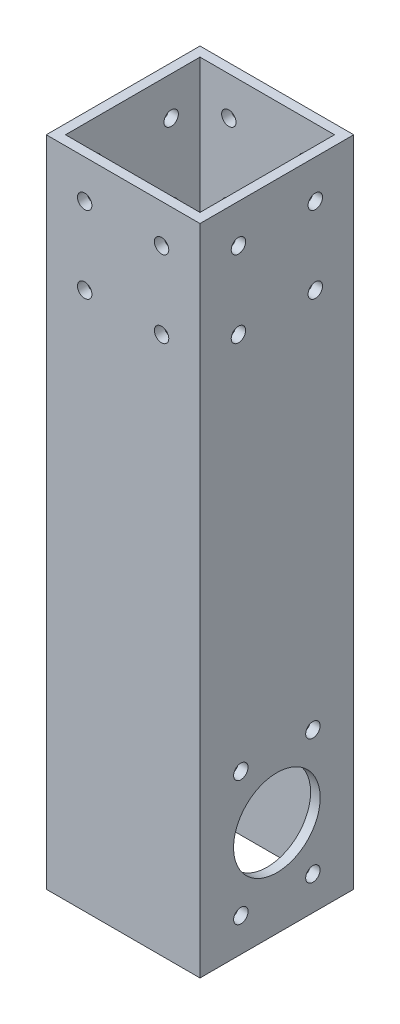
SolidWorks part; units mm, degrees
material "6063-T1"
ref_plane "Front Plane" through (0, 0, 0) normal (0, 0, 1) x (1, 0, 0)
ref_plane "Top Plane" through (0, 0, 0) normal (0, 1, 0) x (1, 0, 0)
ref_plane "Right Plane" through (0, 0, 0) normal (1, 0, 0) x (0, 0, -1)
sketch "Sketch1" plane through (0, 0, 0) normal (0, 1, 0) x (1, 0, 0)
  line L1 (-25.4, 25.4) -> (25.4, 25.4)
  line L2 (-25.4, 25.4) -> (-25.4, -25.4)
  line L3 (-25.4, -25.4) -> (25.4, -25.4)
  line L4 (25.4, 25.4) -> (25.4, -25.4)
  line L5 (-25.4, 25.4) -> (25.4, -25.4) construction
  line L6 (-25.4, -25.4) -> (25.4, 25.4) construction
  point P0 (0, 0)
  dimension "D1" = 50.8
  dimension "D2" = 50.8
extrude "Boss-Extrude1" add sketch "Sketch1" along normal blind 215.9
shell "Shell1" thickness 3.175 removed face at (0, 0, 0) removed face at (0, 215.9, 0)
sketch "Sketch2" plane through (25.4, 0, 0) normal (1, 0, 0) x (0, 0, -1)
  line L0 (-25.4, 0) -> (25.4, 0) construction
  circle A0 centre (0, 31.75) radius 14.3129
  dimension "D1" = 28.6258
  dimension "D2" = 31.75
extrude "Cut-Extrude1" cut sketch "Sketch2" against normal through all
sketch "Sketch3" plane through (25.4, 0, 0) normal (1, 0, 0) x (0, 0, -1)
  line L0 (0, 0) -> (0, 31.75) construction
  line L1 (-25.4, 0) -> (25.4, 0) construction
  line L2 (0, 31.75) -> (-11.9063, 52.3722) construction
  circle A0 centre (0, 31.75) radius 23.8125 construction
  circle A1 centre (-11.9063, 52.3722) radius 2.3812
  circle A2 centre (11.9062, 52.3722) radius 2.3812
  circle A3 centre (23.8125, 31.75) radius 2.3812
  circle A4 centre (11.9063, 11.1278) radius 2.3812
  circle A5 centre (-11.9062, 11.1278) radius 2.3813
  circle A6 centre (-23.8125, 31.75) radius 2.3812
  point P21 (0, 31.75)
  dimension "D1" = 47.625
  dimension "D2" = 4.7625
  dimension "D3" = 150
  dimension "D4" = 6
extrude "Cut-Extrude2" cut sketch "Sketch3" against normal through all contours A1 | A2 | A5 | A4 region at (25.4, 52.3722, 11.9063) region at (25.4, 52.3722, -11.9062) region at (25.4, 11.1278, -11.9063) region at (25.4, 11.1278, 11.9062)
sketch "Sketch4" plane through (25.4, 0, 0) normal (1, 0, 0) x (0, 0, -1)
  line L0 (-25.4, 215.9) -> (25.4, 215.9) construction
  line L1 (-25.4, 215.9) -> (-25.4, 0) construction
  circle A0 centre (-12.7, 203.2) radius 2.3812
  circle A1 centre (12.7, 203.2) radius 2.3812
  circle A2 centre (12.7, 177.8) radius 2.3812
  circle A3 centre (-12.7, 177.8) radius 2.3812
  dimension "D5" = 4.7625
  dimension "D1" = 12.7
  dimension "D2" = 12.7
  dimension "D3" = 2
  dimension "D4" = 2
extrude "Cut-Extrude3" cut sketch "Sketch4" against normal through all
sketch "Sketch5" plane through (0, 0, 25.4) normal (0, 0, 1) x (1, 0, 0)
  line L0 (-25.4, 215.9) -> (25.4, 215.9) construction
  line L1 (-25.4, 215.9) -> (-25.4, 0) construction
  circle A0 centre (-12.7, 203.2) radius 2.3812
  circle A1 centre (12.7, 203.2) radius 2.3812
  circle A2 centre (12.7, 177.8) radius 2.3812
  circle A3 centre (-12.7, 177.8) radius 2.3812
  dimension "D1" = 4.7625
  dimension "D2" = 12.7
  dimension "D3" = 12.7
  dimension "D4" = 2
  dimension "D5" = 2
extrude "Cut-Extrude4" cut sketch "Sketch5" against normal through all
